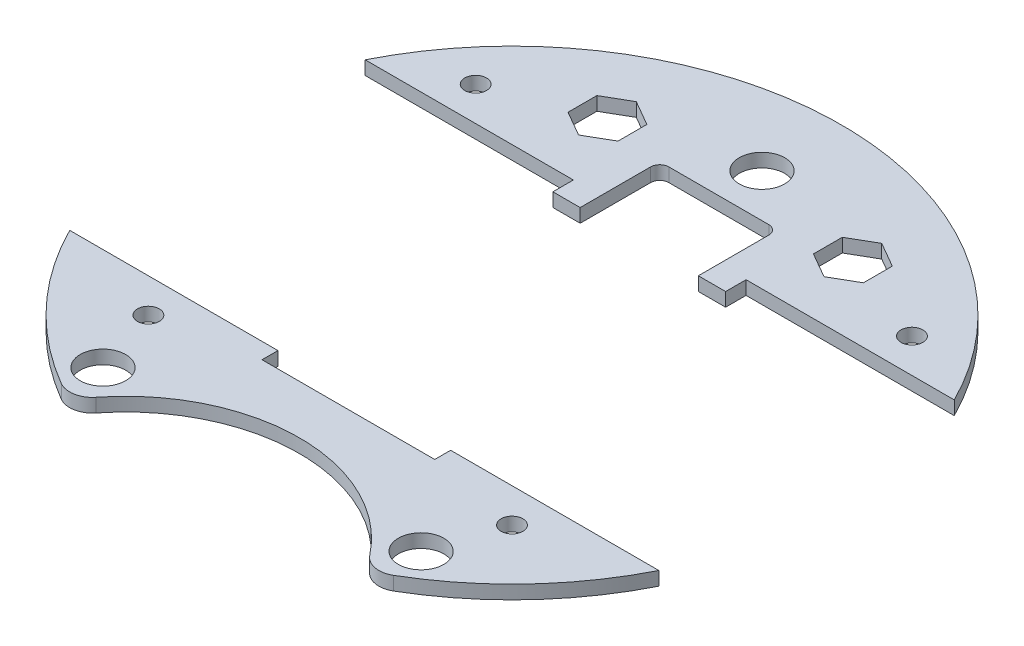
SolidWorks part; units mm, degrees
material "Acrylic (Medium-high impact)"
ref_plane "Front Plane" through (0, 0, 0) normal (0, 0, 1) x (1, 0, 0)
ref_plane "Top Plane" through (0, 0, 0) normal (0, 1, 0) x (1, 0, 0)
ref_plane "Right Plane" through (0, 0, 0) normal (1, 0, 0) x (0, 0, -1)
sketch "Sketch1" plane through (0, 0, 0) normal (0, 1, 0) x (1, 0, 0)
  line L0 (0, -85) -> (-32.4891, -64.8129) construction
  line L1 (0, -85) -> (0, 0) construction
  arc A0 (36.5434, -62.6165) -> (-36.5434, -62.6165) centre (0, 0) ccw
  arc A1 (30.0898, -61.3851) -> (-30.0898, -61.3851) centre (0, -85) ccw
  arc A2 (-30.0898, -61.3851) -> (-36.5434, -62.6165) centre (-34.0231, -58.2982) cw
  arc A3 (36.5434, -62.6165) -> (30.0898, -61.3851) centre (34.0231, -58.2982) cw
  dimension "D1" = 145
  dimension "D2" = 76.5
  dimension "D4" = 5
  dimension "D3" = 85
extrude "Boss-Extrude1" add sketch "Sketch1" along normal blind 3
sketch "solenoid placement" plane through (0, 3, 0) normal (0, 1, 0) x (1, 0, 0)
  line L4 (-19, -36) -> (19, -36)
  line L5 (-19, 28) -> (-19, -36)
  line L6 (19, 28) -> (-19, 28)
  line L7 (19, -36) -> (19, 28)
  line L8 (-19, -36) -> (19, -36)
  line L9 (-19, 28) -> (-19, -36)
  line L10 (19, 28) -> (-19, 28)
  line L11 (19, -36) -> (19, 28)
  dimension "D1" = 0
extrude "Cut-Extrude1" cut sketch "solenoid placement" against normal through all
sketch "Sketch4" plane through (0, 3, 0) normal (0, 1, 0) x (1, 0, 0)
  line L8 (13, 28) -> (13, 43.5)
  line L9 (-13, 28) -> (13, 28)
  line L10 (-13, 43.5) -> (-13, 28)
  line L11 (11, 45.5) -> (-11, 45.5)
  line L28 (13, 28) -> (13, 43.5)
  line L29 (-13, 28) -> (13, 28)
  line L30 (-13, 43.5) -> (-13, 28)
  line L31 (11, 45.5) -> (-11, 45.5)
  arc A4 (-11, 45.5) -> (-13, 43.5) centre (-11, 43.5) ccw
  arc A5 (13, 43.5) -> (11, 45.5) centre (11, 43.5) ccw
  arc A14 (-11, 45.5) -> (-13, 43.5) centre (-11, 43.5) ccw
  arc A15 (13, 43.5) -> (11, 45.5) centre (11, 43.5) ccw
  dimension "D1" = 0
extrude "Cut-Extrude4" cut sketch "Sketch4" against normal through all
sketch "Sketch5" plane through (0, 3, 0) normal (0, 1, 0) x (1, 0, 0)
  line L12 (-21.5, 51.1754) -> (-27, 54.3509)
  line L13 (-27, 54.3509) -> (-32.5, 51.1754)
  line L14 (-32.5, 51.1754) -> (-32.5, 44.8246)
  line L15 (-32.5, 44.8246) -> (-27, 41.6491)
  line L16 (-27, 41.6491) -> (-21.5, 44.8246)
  line L17 (-21.5, 44.8246) -> (-21.5, 51.1754)
  line L18 (-21.5, 51.1754) -> (-27, 54.3509)
  line L19 (-27, 54.3509) -> (-32.5, 51.1754)
  line L20 (-32.5, 51.1754) -> (-32.5, 44.8246)
  line L21 (-32.5, 44.8246) -> (-27, 41.6491)
  line L22 (-27, 41.6491) -> (-21.5, 44.8246)
  line L23 (-21.5, 44.8246) -> (-21.5, 51.1754)
  line L24 (21.5, 51.1754) -> (21.5, 44.8246)
  line L25 (21.5, 44.8246) -> (27, 41.6491)
  line L26 (27, 41.6491) -> (32.5, 44.8246)
  line L27 (32.5, 44.8246) -> (32.5, 51.1754)
  line L28 (32.5, 51.1754) -> (27, 54.3509)
  line L29 (27, 54.3509) -> (21.5, 51.1754)
  line L42 (21.5, 51.1754) -> (21.5, 44.8246)
  line L43 (21.5, 44.8246) -> (27, 41.6491)
  line L44 (27, 41.6491) -> (32.5, 44.8246)
  line L45 (32.5, 44.8246) -> (32.5, 51.1754)
  line L46 (32.5, 51.1754) -> (27, 54.3509)
  line L47 (27, 54.3509) -> (21.5, 51.1754)
  dimension "D1" = 0
  dimension "D2" = 0
extrude "Cut-Extrude5" cut sketch "Sketch5" against normal through all
sketch "Sketch6" plane through (0, 3, 0) normal (0, 1, 0) x (1, 0, 0)
  circle A1 centre (40, -40) radius 2.4
  circle A2 centre (40, -40) radius 2.4
  circle A3 centre (-40, -40) radius 2.4
  circle A4 centre (-40, -40) radius 2.4
  circle A5 centre (48, 40) radius 2.4
  circle A6 centre (48, 40) radius 2.4
  circle A7 centre (-48, 40) radius 2.4
  circle A8 centre (-48, 40) radius 2.4
  dimension "D1" = 0
  dimension "D2" = 0
  dimension "D3" = 0
  dimension "D4" = 0
extrude "Cut-Extrude6" cut sketch "Sketch6" against normal through all
sketch "Sketch3" plane through (0, 3, 0) normal (0, 1, 0) x (1, 0, 0)
  line L0 (-19, 28) -> (-19, 32.5)
  line L1 (72.5, -32.5) -> (-72.5, -32.5)
  line L2 (72.5, -32.5) -> (72.5, 32.5)
  line L3 (72.5, 32.5) -> (19, 32.5)
  line L4 (-72.5, -32.5) -> (-72.5, 32.5)
  line L5 (72.5, -32.5) -> (-72.5, 32.5) construction
  line L6 (72.5, 32.5) -> (-72.5, -32.5) construction
  line L7 (-19, 28) -> (19, 28)
  line L8 (19, 28) -> (19, 32.5)
  line L9 (-19, 32.5) -> (-72.5, 32.5)
  line L10 (-19, 28) -> (-19, -36) construction
  line L11 (-13, 28) -> (-19, 28) construction
  arc A0 (36.5434, -62.6165) -> (-36.5434, -62.6165) centre (0, 0) ccw construction
  point P0 (0, 0)
  dimension "D1" = 65
extrude "Cut-Extrude3" cut sketch "Sketch3" against normal through all
sketch "Sketch7" plane through (0, 3, 0) normal (0, 1, 0) x (1, 0, 0)
  circle A1 centre (35, -55) radius 5
  circle A2 centre (35, -55) radius 5
  circle A3 centre (-35, -55) radius 5
  circle A4 centre (-35, -55) radius 5
  dimension "D1" = 0
  dimension "D2" = 0
extrude "Cut-Extrude7" cut sketch "Sketch7" against normal through all
sketch "Sketch8" plane through (0, 3, 0) normal (0, -1, 0) x (1, 0, 0)
  circle A1 centre (0, -55) radius 5
  circle A2 centre (0, -55) radius 5
  dimension "D1" = 0
extrude "Cut-Extrude9" cut sketch "Sketch8" along normal through all
equation "\"smallPulleyTeeth\"= 30"
equation "\"largePulleyTeeth\"= 30"
equation "\"eighthThick\"= 3.0mm"
equation "\"sixteenthThick\"= 1.7mm"
equation "\"quarterThick\"=6.0mm"
equation "\"OD\"= 145mm"
equation "\"puckAngle\"= 60.5deg"
equation "\"D1@Sketch1\"=\"OD\""
equation "\"puckDiam\"= 76.5mm"
equation "\"D2@Sketch1\"=\"puckDiam\""
equation "\"D1@Boss-Extrude1\"=\"eighthThick\""
equation "\"axlePress\"= 5.9mm"
equation "\"press\"= 0.2mm"
equation "\"wheelClear\"= 0.3mm"
equation "\"10-32clear\"= 4.8mm"
equation "\"6-32clear\"= 3.3mm"
equation "\"8-32clear\"= 4.0mm"
equation "\"wheelHeight\"= 22mm"
equation "\"wheelWell\"= 65mm"
equation "\"D1@Sketch3\"=\"wheelWell\""
equation "\"puckDist\"= 85mm"
equation "\"scoopFillet\"= 5mm"
equation "\"4-40clear\"= 3.0mm"
equation "\"D3@Sketch1\"=\"puckDist\""
equation "\"D4@Sketch1\"=\"scoopFillet\""
